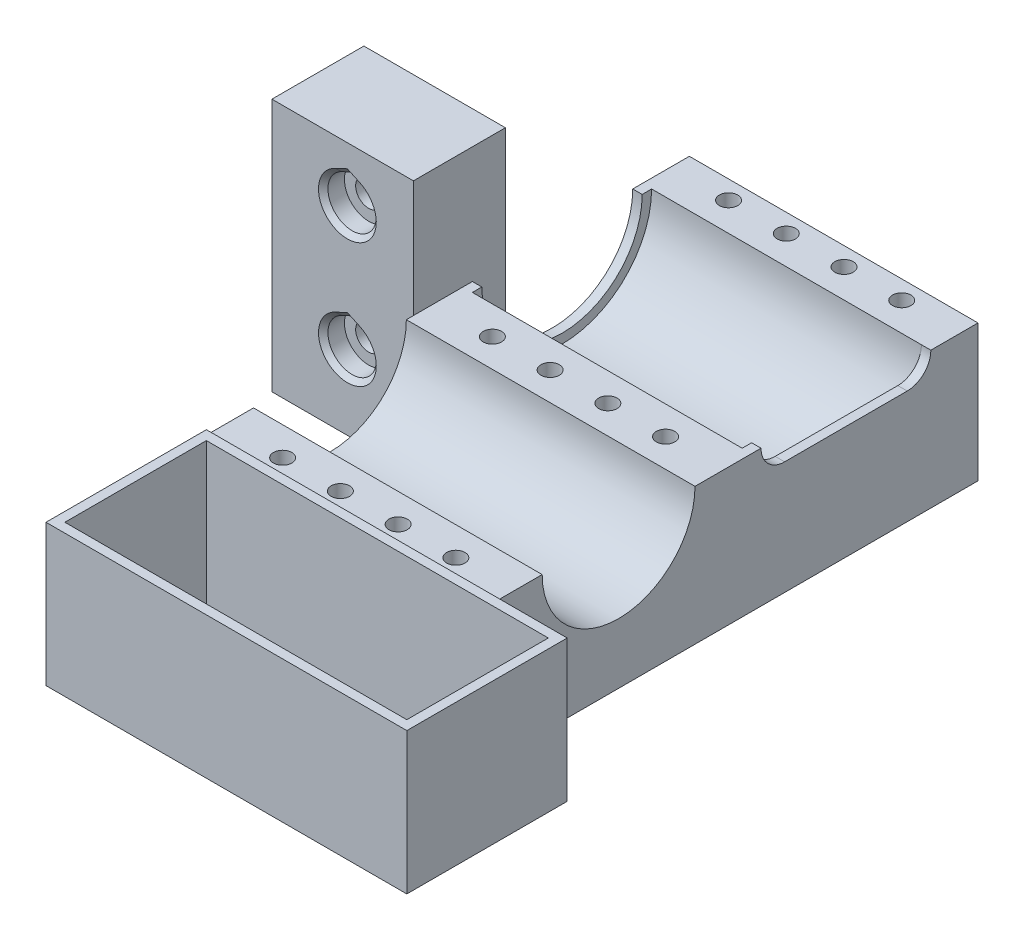
SolidWorks part; units mm, degrees
ref_plane "Front Plane" through (0, 0, 0) normal (0, 0, 1) x (1, 0, 0)
ref_plane "Top Plane" through (0, 0, 0) normal (0, 1, 0) x (1, 0, 0)
ref_plane "Right Plane" through (0, 0, 0) normal (1, 0, 0) x (0, 0, -1)
sketch "Sketch1" plane through (0, 0, 0) normal (1, 0, 0) x (0, 0, -1)
  line L0 (51.2, 42.0261) -> (51.2, 0) construction
  line L1 (0, 0) -> (102.4, 0)
  line L2 (0, 0) -> (0, 29)
  line L3 (102.4, 0) -> (102.4, 29)
  line L4 (0, 29) -> (10, 29) construction
  line L6 (42.4, 29) -> (54.4, 29) construction
  line L7 (42.4, 29) -> (54.4, 29)
  line L8 (0, 29) -> (10, 29)
  line L10 (42.4, 29) -> (54.4, 29)
  line L11 (92.4, 29) -> (102.4, 29)
  arc A0 (10, 29) -> (42.4, 29) centre (26.2, 29) ccw
  arc A1 (54.4, 29) -> (92.4, 29) centre (73.4, 29) ccw
  point P15 (73.4, 10)
  dimension "D3" = 19
  dimension "D4" = 16.2
  dimension "D1" = 10
  dimension "D2" = 12
  dimension "D5" = 10
extrude "Boss-Extrude1" add sketch "Sketch1" along normal blind 61.2 contours L8 L2 L1 L3 L7 region at (0, 11.0871, -50.0531)
sketch "Sketch7" plane through (0, 0, 0) normal (-1, 0, 0) x (0, 0, 1)
  line L0 (0, 0) -> (-102.4, 0) construction
  line L1 (-63.4, 0) -> (-43.8992, 0)
  line L2 (-63.4, 0) -> (-63.4, 53.7409)
  line L3 (-63.4, 53.7409) -> (-43.8992, 53.7409)
  line L4 (-43.8992, 0) -> (-43.8992, 53.7409)
  line L5 (-42.4, 29) -> (-54.4, 29) construction
  line L6 (-42.4, 29) -> (-54.4, 29) construction
  arc A0 (-92.4, 29) -> (-54.4, 29) centre (-73.4, 29) ccw construction
  arc A1 (-92.4, 29) -> (-54.4, 29) centre (-73.4, 29) ccw construction
  circle A2 centre (-73.4, 29) radius 6 construction
  dimension "D1" = 12
  dimension "D2" = 10
  dimension "D3" = 1.4992
extrude "Boss-Extrude2" add sketch "Sketch7" along normal blind 30
sketch "Sketch14" plane through (61.2, 0, 0) normal (1, 0, 0) x (0, 0, -1)
  line L0 (54.4, 29) -> (92.4, 29)
  arc A0 (54.4, 29) -> (92.4, 29) centre (73.4, 29) ccw construction
  arc A1 (54.4, 29) -> (92.4, 29) centre (73.4, 29) ccw
extrude "Boss-Extrude3" add sketch "Sketch14" against normal blind 2
sketch "Sketch19" plane through (0, 0, 0) normal (-1, 0, 0) x (0, 0, 1)
  line L1 (-90.4, 29) -> (-92.4, 29)
  line L2 (-56.4, 29) -> (-54.4, 29)
  arc A5 (-63.4, 12.8445) -> (-54.4, 29) centre (-73.4, 29) ccw construction
  arc A7 (-92.4, 29) -> (-63.4, 12.8445) centre (-73.4, 29) ccw construction
  arc A8 (-63.4, 12.8445) -> (-54.4, 29) centre (-73.4, 29) ccw
  arc A9 (-92.4, 29) -> (-63.4, 12.8445) centre (-73.4, 29) ccw
  arc A10 (-90.4, 29) -> (-64.4526, 14.5451) centre (-73.4, 29) ccw
  arc A11 (-64.4526, 14.5451) -> (-56.4, 29) centre (-73.4, 29) ccw
  dimension "D1" = 2
extrude "Boss-Extrude4" add sketch "Sketch19" against normal blind 2
sketch "Sketch26" plane through (0, 0, 0) normal (0, 1, 0) x (1, 0, 0)
  line L0 (2, -2) -> (74.5, -2)
  line L1 (0, 0) -> (76.5, 0)
  line L2 (0, 0) -> (0, -34)
  line L3 (0, -34) -> (76.5, -34)
  line L4 (76.5, 0) -> (76.5, -34)
  line L5 (74.5, -2) -> (74.5, -32)
  line L6 (2, -32) -> (74.5, -32)
  line L7 (2, -2) -> (2, -32)
  dimension "D1" = 34
  dimension "D2" = 76.5
  dimension "D3" = 2
extrude "Boss-Extrude5" add sketch "Sketch26" along normal blind 30
sketch "Sketch8" plane through (0, 0, -63.4) normal (0, 0, -1) x (-1, 0, 0)
  line L0 (30, 53.7409) -> (0, 53.7409) construction
  line L1 (0, 53.7409) -> (0, 15.2523) construction
  line L2 (30, 53.7409) -> (0, 53.7409) construction
  line L3 (0, 53.7409) -> (0, 15.2523) construction
  line L5 (-2, 29) -> (0, 29) construction
  line L6 (12.485, 44.4951) -> (14, 45.4951)
  line L7 (14, 45.4951) -> (15.515, 44.4951)
  line L8 (12.485, 44.4951) -> (15.515, 44.4951) construction
  line L9 (14, 19.0951) -> (12.485, 18.0951)
  line L10 (14, 19.0951) -> (15.515, 18.0951)
  line L11 (15.515, 18.0951) -> (12.485, 18.0951) construction
  line L12 (3.5, 29) -> (45.8321, 29) construction
  line L14 (-2, 29) -> (-2, 10) construction
  line L15 (-2, 29) -> (-2, 10) construction
  line L16 (-2, 29) -> (0, 29) construction
  arc A0 (12.485, 44.4951) -> (15.515, 44.4951) centre (14, 42.2) ccw
  arc A1 (12.485, 18.0951) -> (15.515, 18.0951) centre (14, 15.8) ccw
  dimension "D3" = 5.5
  dimension "D2" = 14
  dimension "D5" = 1
  dimension "D6" = 1
  dimension "D1" = 13.2
  dimension "D4" = 13.2
extrude "Cut-Extrude1" cut sketch "Sketch8" against normal up to surface (19.5008 mm away) up to face at (-12, 27.2964, -43.8992)
sketch "Sketch9" plane through (0, 0, -63.4) normal (0, 0, -1) x (-1, 0, 0)
  line L0 (11.8438, 46.8493) -> (14, 47.8493)
  line L1 (14, 47.8493) -> (16.1562, 46.8493)
  line L2 (11.8438, 46.8493) -> (16.1562, 46.8493) construction
  line L3 (11.8438, 20.4493) -> (14, 21.4493)
  line L4 (14, 21.4493) -> (16.1562, 20.4493)
  line L5 (11.8438, 20.4493) -> (16.1562, 20.4493) construction
  arc A0 (11.8438, 46.8493) -> (16.1562, 46.8493) centre (14, 42.2) ccw
  arc A1 (11.8438, 20.4493) -> (16.1562, 20.4493) centre (14, 15.8) ccw
  dimension "D1" = 10.25
  dimension "D2" = 1
  dimension "D3" = 1
extrude "Cut-Extrude2" cut sketch "Sketch9" against normal blind 4.5
sketch "Sketch10" plane through (0, 0, -43.8992) normal (0, 0, 1) x (1, 0, 0)
  line L0 (-16.1562, 46.8493) -> (-14, 47.8493)
  line L1 (-14, 47.8493) -> (-11.8438, 46.8493)
  line L2 (-16.1562, 46.8493) -> (-11.8438, 46.8493) construction
  line L3 (-16.1562, 20.4493) -> (-14, 21.4493)
  line L4 (-14, 21.4493) -> (-11.8438, 20.4493)
  line L5 (-16.1562, 20.4493) -> (-11.8438, 20.4493) construction
  arc A0 (-16.1562, 46.8493) -> (-11.8438, 46.8493) centre (-14, 42.2) ccw
  arc A1 (-16.1562, 20.4493) -> (-11.8438, 20.4493) centre (-14, 15.8) ccw
  dimension "D1" = 10.25
  dimension "D2" = 1
  dimension "D3" = 1
extrude "Cut-Extrude8" cut sketch "Sketch10" against normal blind 4.5
sketch "Sketch22" plane through (0, 29, 0) normal (0, 1, 0) x (1, 0, 0)
  line L0 (61.2, 42.4) -> (0, 42.4) construction
  line L1 (59.2, 54.4) -> (2, 54.4) construction
  line L2 (61.2, 42.4) -> (0, 42.4) construction
  line L3 (59.2, 54.4) -> (2, 54.4) construction
  line L4 (30.6, 54.4) -> (30.6, 42.4) construction
  line L5 (30.6, 48.4) -> (0, 48.4) construction
  line L6 (30.6, 48.4) -> (61.2, 48.4) construction
  line L7 (61.2, 42.4) -> (61.2, 102.4) construction
  line L8 (61.2, 10) -> (61.2, 42.4) construction
  line L9 (59.2, 92.4) -> (59.2, 54.4) construction
  line L10 (61.2, 10) -> (61.2, 42.4) construction
  line L11 (59.2, 92.4) -> (59.2, 54.4) construction
  line L12 (59.2, 73.4) -> (-4.6102, 73.4) construction
  line L13 (61.2, 26.2) -> (-9.4707, 26.2) construction
  line L14 (-21.9217, 98.47) -> (51.6485, 98.47) construction
  line L15 (76.5, 0) -> (0, 0) construction
  line L16 (10.6744, 3.93) -> (59.5979, 3.93) construction
  line L17 (0, 43.8992) -> (0, 63.4) construction
  line L18 (61.2, 102.4) -> (0, 102.4) construction
  line L19 (0, 43.8992) -> (0, 63.4) construction
  circle A0 centre (12.24, 48.4) radius 1.95
  circle A1 centre (24.48, 48.4) radius 1.95
  circle A2 centre (36.72, 48.4) radius 1.95
  circle A3 centre (48.96, 48.4) radius 1.95
  circle A5 centre (48.96, 98.47) radius 1.95
  circle A8 centre (24.48, 98.47) radius 1.95
  circle A9 centre (12.24, 98.47) radius 1.95
  circle A10 centre (36.72, 3.93) radius 1.95
  circle A11 centre (48.96, 3.93) radius 1.95
  circle A14 centre (12.24, 3.93) radius 1.95
  circle A15 centre (36.72, 98.47) radius 1.95
  circle A16 centre (24.48, 3.93) radius 1.95
  point P40 (-10.8, 48.4)
  point P41 (-10.8, 48.4)
  point P42 (0, 48.4)
  point P43 (0, 0)
  point P55 (0, 0)
  dimension "D1" = 3.9
  dimension "D7" = 3.93
  dimension "D8" = 3.93
  dimension "D2" = 12.24
  dimension "D3" = 61.2
  dimension "D4" = 12.24
  dimension "D5" = 12.24
  dimension "D6" = 12.24
extrude "Cut-Extrude9" cut sketch "Sketch22" against normal up to surface (29 mm away) up to face at (21.54, 0, -35.1398)
sketch "Sketch24" plane through (0, 0, 0) normal (0, -1, 0) x (1, 0, 0)
  line L0 (74.5, 2) -> (2, 2) construction
  line L1 (15.7041, -3.93) -> (13.9721, -0.93)
  line L2 (13.9721, -0.93) -> (10.5079, -0.93)
  line L3 (10.5079, -0.93) -> (8.7759, -3.93)
  line L4 (8.7759, -3.93) -> (10.5079, -6.93)
  line L5 (10.5079, -6.93) -> (13.9721, -6.93)
  line L6 (13.9721, -6.93) -> (15.7041, -3.93)
  line L7 (27.9441, -3.93) -> (26.2121, -0.93)
  line L8 (26.2121, -0.93) -> (22.7479, -0.93)
  line L9 (22.7479, -0.93) -> (21.0159, -3.93)
  line L10 (21.0159, -3.93) -> (22.7479, -6.93)
  line L11 (22.7479, -6.93) -> (26.2121, -6.93)
  line L12 (26.2121, -6.93) -> (27.9441, -3.93)
  line L13 (40.1841, -3.93) -> (38.4521, -0.93)
  line L14 (38.4521, -0.93) -> (34.9879, -0.93)
  line L15 (34.9879, -0.93) -> (33.2559, -3.93)
  line L16 (33.2559, -3.93) -> (34.9879, -6.93)
  line L17 (34.9879, -6.93) -> (38.4521, -6.93)
  line L18 (38.4521, -6.93) -> (40.1841, -3.93)
  line L19 (52.4241, -3.93) -> (50.6921, -0.93)
  line L20 (50.6921, -0.93) -> (47.2279, -0.93)
  line L21 (47.2279, -0.93) -> (45.4959, -3.93)
  line L22 (45.4959, -3.93) -> (47.2279, -6.93)
  line L23 (47.2279, -6.93) -> (50.6921, -6.93)
  line L24 (50.6921, -6.93) -> (52.4241, -3.93)
  line L25 (45.4959, -48.4009) -> (47.2287, -51.4005)
  line L26 (47.2287, -51.4005) -> (50.6928, -51.3995)
  line L27 (50.6928, -51.3995) -> (52.4241, -48.3991)
  line L28 (52.4241, -48.3991) -> (50.6913, -45.3995)
  line L29 (50.6913, -45.3995) -> (47.2272, -45.4005)
  line L30 (47.2272, -45.4005) -> (45.4959, -48.4009)
  line L31 (33.2559, -48.4007) -> (34.9885, -51.4003)
  line L32 (34.9885, -51.4003) -> (38.4526, -51.3997)
  line L33 (38.4526, -51.3997) -> (40.1841, -48.3993)
  line L34 (40.1841, -48.3993) -> (38.4515, -45.3997)
  line L35 (38.4515, -45.3997) -> (34.9874, -45.4003)
  line L36 (34.9874, -45.4003) -> (33.2559, -48.4007)
  line L37 (21.0159, -48.4005) -> (22.7484, -51.4003)
  line L38 (22.7484, -51.4003) -> (26.2125, -51.3997)
  line L39 (26.2125, -51.3997) -> (27.9441, -48.3995)
  line L40 (27.9441, -48.3995) -> (26.2116, -45.3997)
  line L41 (26.2116, -45.3997) -> (22.7475, -45.4003)
  line L42 (22.7475, -45.4003) -> (21.0159, -48.4005)
  line L43 (8.7759, -48.4005) -> (10.5083, -51.4002)
  line L44 (10.5083, -51.4002) -> (13.9724, -51.3998)
  line L45 (13.9724, -51.3998) -> (15.7041, -48.3995)
  line L46 (15.7041, -48.3995) -> (13.9717, -45.3998)
  line L47 (13.9717, -45.3998) -> (10.5076, -45.4002)
  line L48 (10.5076, -45.4002) -> (8.7759, -48.4005)
  line L49 (10.5079, -95.47) -> (8.7759, -98.47)
  line L50 (8.7759, -98.47) -> (10.5079, -101.47)
  line L51 (10.5079, -101.47) -> (13.9721, -101.47)
  line L52 (13.9721, -101.47) -> (15.7041, -98.47)
  line L53 (15.7041, -98.47) -> (13.9721, -95.47)
  line L54 (13.9721, -95.47) -> (10.5079, -95.47)
  line L55 (22.7479, -95.47) -> (21.0159, -98.47)
  line L56 (21.0159, -98.47) -> (22.7479, -101.47)
  line L57 (22.7479, -101.47) -> (26.2121, -101.47)
  line L58 (26.2121, -101.47) -> (27.9441, -98.47)
  line L59 (27.9441, -98.47) -> (26.2121, -95.47)
  line L60 (26.2121, -95.47) -> (22.7479, -95.47)
  line L61 (34.9879, -95.47) -> (33.2559, -98.47)
  line L62 (33.2559, -98.47) -> (34.9879, -101.47)
  line L63 (34.9879, -101.47) -> (38.4521, -101.47)
  line L64 (38.4521, -101.47) -> (40.1841, -98.47)
  line L65 (40.1841, -98.47) -> (38.4521, -95.47)
  line L66 (38.4521, -95.47) -> (34.9879, -95.47)
  line L67 (47.2279, -95.47) -> (45.4959, -98.47)
  line L68 (45.4959, -98.47) -> (47.2279, -101.47)
  line L69 (47.2279, -101.47) -> (50.6921, -101.47)
  line L70 (50.6921, -101.47) -> (52.4241, -98.47)
  line L71 (52.4241, -98.47) -> (50.6921, -95.47)
  line L72 (50.6921, -95.47) -> (47.2279, -95.47)
  line L73 (61.2, -102.4) -> (0, -102.4) construction
  circle A0 centre (12.24, -3.93) radius 3 construction
  circle A1 centre (24.48, -3.93) radius 3 construction
  circle A2 centre (36.72, -3.93) radius 3 construction
  circle A3 centre (48.96, -3.93) radius 3 construction
  circle A4 centre (48.96, -48.4) radius 3 construction
  circle A5 centre (36.72, -48.4) radius 3 construction
  circle A6 centre (24.48, -48.4) radius 3 construction
  circle A7 centre (12.24, -48.4) radius 3 construction
  circle A8 centre (12.24, -98.47) radius 3 construction
  circle A9 centre (24.48, -98.47) radius 3 construction
  circle A10 centre (36.72, -98.47) radius 3 construction
  circle A11 centre (48.96, -98.47) radius 3 construction
  dimension "D1" = 6
extrude "Cut-Extrude10" cut sketch "Sketch24" against normal blind 4.5
sketch "Sketch25" plane through (61.2, 0, 0) normal (1, 0, 0) x (0, 0, -1)
  line L0 (61.4, 29) -> (87.4, 29) construction
  line L1 (42.4, 29) -> (102.4, 29) construction
  line L2 (61.4, 34) -> (87.4, 34)
  line L3 (61.4, 24) -> (87.4, 24)
  line L6 (92.4, 29) -> (54.4, 29) construction
  line L7 (92.4, 29) -> (54.4, 29) construction
  arc A0 (61.4, 34) -> (61.4, 24) centre (61.4, 29) ccw
  arc A1 (87.4, 24) -> (87.4, 34) centre (87.4, 29) ccw
  point P5 (74.4, 29)
  point P12 (92.4, 29)
  dimension "D1" = 10
extrude "Cut-Extrue11" cut sketch "Sketch25" against normal blind 2
chamfer "Chamfer1" distance 1 angle 45 12 edges at (-15.0781, 20.9493, -43.8992) (-12.9219, 20.9493, -43.8992) (-14, 10.675, -43.8992) (-15.0781, 47.3493, -43.8992) (-12.9219, 47.3493, -43.8992) (-14, 37.075, -43.8992) (-12.9219, 20.9493, -63.4) (-15.0781, 20.9493, -63.4) (-14, 10.675, -63.4) (-12.9219, 47.3493, -63.4) (-15.0781, 47.3493, -63.4) (-14, 37.075, -63.4)
split "Split1" bodies to split 126 resulting bodies 128 129 split by face at (0, 35.9789, -53.8698)
equation "\"MotorDIA\"= 37' Motor Diameter"
equation "\"SyringeDIA\"= 31.4'60ml Syringe Diameter"
equation "\"MotorShaftDIA\"= 6'Motor Shaft Dia"
equation "\"MotorKeyway\"= 1'Motor Shaft Keyway Depth"
equation "\"MotorLength\"= 56.7'Motor Length Excluding Shaft"
equation "\"SyringeLength\"= 117.3'60ml Syringe Length Excluding Nozzle"
equation "\"3Dtol\"= .5'Sizing Tolerance for 3D printed parts"
equation "\"ChamberDIA\"= 100 - 4'Buoyancy Chamber inner Diameter"
equation "\"ChamberThk\"= 2mm'Buoyancy Chamber Wall Thickness"
equation "\"D4@Sketch1\"=\"SyringeDIA\"/2+\"3Dtol\""
equation "\"D3@Sketch1\"=\"MotorDIA\"/2+\"3Dtol\""
equation "\"D1@Boss-Extrude1\"=\"MotorLength\"+\"3Dtol\"+4"
equation "\"D4@Sketch8\"=\"D1@Sketch8\""
equation "\"BearingOD\"= 10"
equation "\"BearingID\"= 4"
equation "\"Bearingwidth\"= 4"
equation "\"ShaftDIA\"= 4"
equation "\"D2@Sketch22\"=\"D3@Sketch22\"/5"
equation "\"D4@Sketch22\"=\"D2@Sketch22\""
equation "\"D5@Sketch22\"=\"D4@Sketch22\""
equation "\"D6@Sketch22\"=\"D5@Sketch22\""
